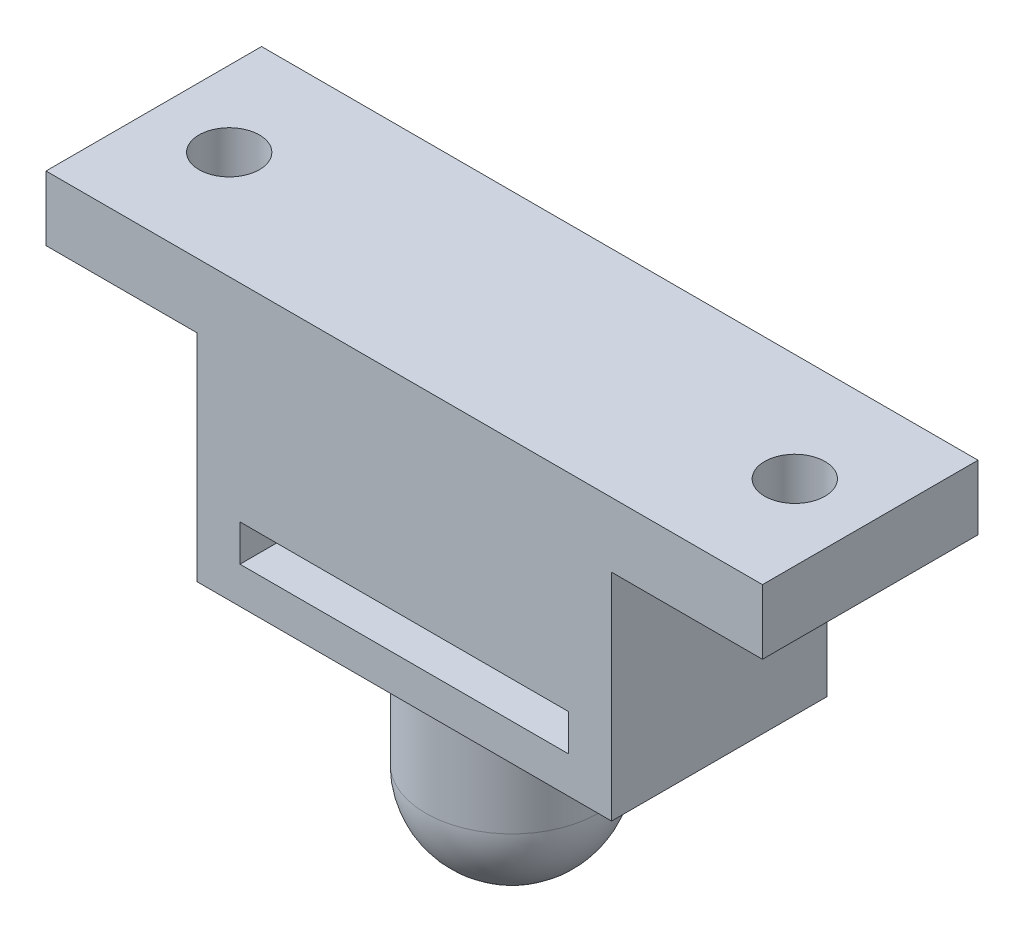
SolidWorks part; units mm, degrees
ref_plane "Front Plane" through (0, 0, 0) normal (0, 0, 1) x (1, 0, 0)
ref_plane "Top Plane" through (0, 0, 0) normal (0, 1, 0) x (1, 0, 0)
ref_plane "Right Plane" through (0, 0, 0) normal (1, 0, 0) x (0, 0, -1)
sketch "Sketch1" plane through (0, 0, 0) normal (0, 1, 0) x (1, 0, 0)
  line L1 (-9.62, -5) -> (9.62, -5)
  line L2 (-9.62, -5) -> (-9.62, 5)
  line L3 (-9.62, 5) -> (9.62, 5)
  line L4 (9.62, -5) -> (9.62, 5)
  line L5 (-9.62, -5) -> (9.62, 5) construction
  line L6 (-9.62, 5) -> (9.62, -5) construction
  line L7 (-9.62, 5) -> (-16.62, 5)
  line L8 (-9.62, 5) -> (-9.62, -5)
  line L9 (-9.62, -5) -> (-16.62, -5)
  line L10 (-16.62, 5) -> (-16.62, -5)
  line L11 (9.62, 5) -> (16.62, 5)
  line L12 (9.62, 5) -> (9.62, -5)
  line L13 (9.62, -5) -> (16.62, -5)
  line L14 (16.62, 5) -> (16.62, -5)
  point P0 (0, 0)
  dimension "D1" = 19.24
  dimension "D2" = 10
  dimension "D3" = 7
extrude "Boss-Extrude1" add sketch "Sketch1" against normal blind 3 contours L7 L10 L9 L2 | L14 L11 L4 L13 region at (-13.12, 0, 0) region at (13.12, 0, 0)
extrude "Boss-Extrude2" add sketch "Sketch1<4>" against normal blind 13 contours L1 L4 L3 L2 region at (0, 0, 0)
sketch "Sketch1<4>" plane through (0, 0, 0) normal (0, 1, 0) x (1, 0, 0) same geometry as "Sketch1"
sketch "Sketch2" plane through (0, 0, 5) normal (0, 0, 1) x (1, 0, 0)
  line L0 (0, -55) -> (0, 55) construction
  line L1 (-7.62, -11.3) -> (7.62, -11.3)
  line L2 (-7.62, -11.3) -> (-7.62, -9.6)
  line L3 (-7.62, -9.6) -> (7.62, -9.6)
  line L4 (7.62, -11.3) -> (7.62, -9.6)
  line L5 (-7.62, -11.3) -> (7.62, -9.6) construction
  line L6 (-7.62, -9.6) -> (7.62, -11.3) construction
  line L7 (55, 0) -> (-55, 0) construction
  point P0 (0, -10.45)
  dimension "D1" = 9.6
  dimension "D2" = 1.7
  dimension "D3" = 15.24
extrude "Cut-Extrude1" cut sketch "Sketch2" against normal blind 14
sketch "Sketch3" plane through (0, -13, 0) normal (0, -1, 0) x (1, 0, 0)
  circle A0 centre (0, 0) radius 4
  dimension "D1" = 8
extrude "Boss-Extrude3" add sketch "Sketch3" along normal blind 9
fillet "Fillet1" radius 4 1 edges at (0, -22, -4)
sketch "Sketch4" plane through (0, 0, 0) normal (0, 1, 0) x (1, 0, 0)
  line L0 (-12.1, 0) -> (12.1, 0) construction
  line L1 (-16.62, 5) -> (-16.62, -5) construction
  line L2 (16.62, 5) -> (16.62, -5) construction
  line L4 (-15.62, 1.4434) -> (-15.62, -1.4434)
  line L5 (-15.62, -1.4434) -> (-13.12, -2.8868)
  line L6 (-13.12, -2.8868) -> (-10.62, -1.4434)
  line L7 (-10.62, -1.4434) -> (-10.62, 1.4434)
  line L8 (-10.62, 1.4434) -> (-13.12, 2.8868)
  line L9 (-13.12, 2.8868) -> (-15.62, 1.4434)
  line L10 (10.62, 1.4434) -> (10.62, -1.4434)
  line L11 (10.62, -1.4434) -> (13.12, -2.8868)
  line L12 (13.12, -2.8868) -> (15.62, -1.4434)
  line L13 (15.62, -1.4434) -> (15.62, 1.4434)
  line L14 (15.62, 1.4434) -> (13.12, 2.8868)
  line L15 (13.12, 2.8868) -> (10.62, 1.4434)
  circle A0 centre (-13.12, 0) radius 1.4
  circle A1 centre (13.12, 0) radius 1.4
  circle A2 centre (-13.12, 0) radius 2.5 construction
  circle A3 centre (13.12, 0) radius 2.5 construction
  dimension "D1" = 2.8
  dimension "D2" = 2.8
  dimension "D3" = 3.5
  dimension "D4" = 3.5
  dimension "D5" = 5
  dimension "D6" = 5
extrude "Cut-Extrude2" cut sketch "Sketch4" against normal up to next contours A0 | A1 region at (-13.12, 0, 0) region at (13.12, 0, 0)
extrude "Cut-Extrude3" cut sketch "Sketch4<3>" against normal up to next from offset 2 offset against normal yes
sketch "Sketch4<3>" plane through (0, 0, 0) normal (0, 1, 0) x (1, 0, 0) same geometry as "Sketch4"
